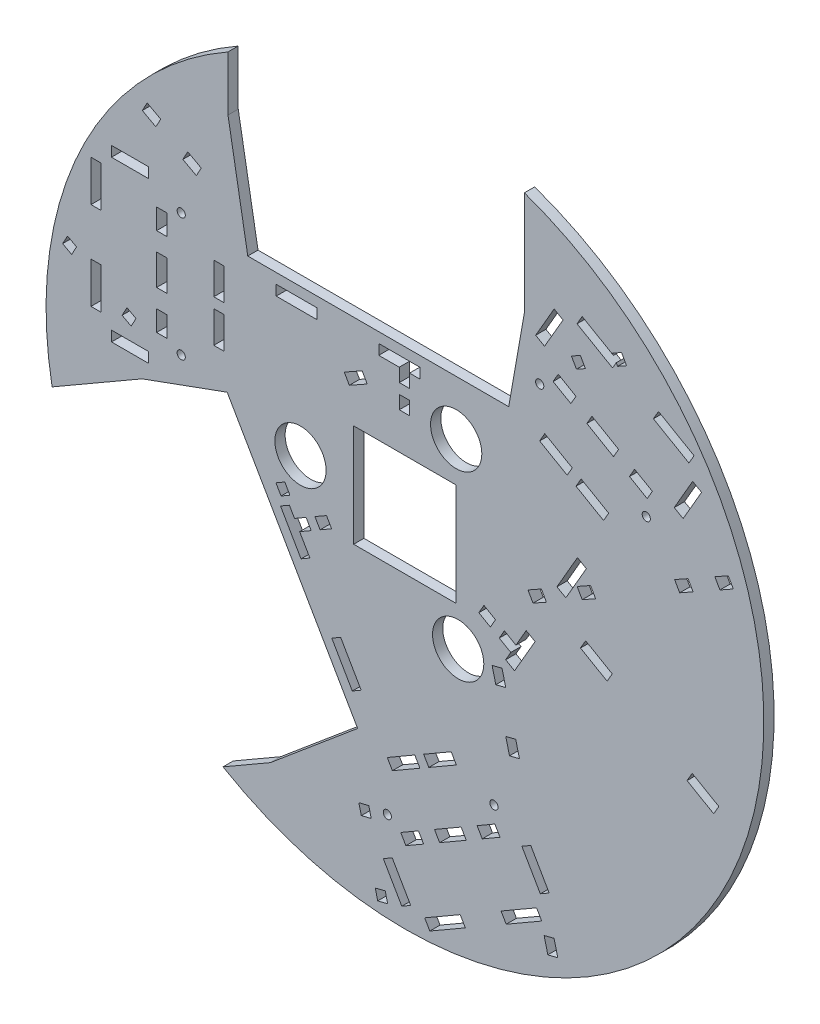
SolidWorks part; units mm, degrees
material "Balsa"
ref_plane "Plan de face" through (0, 0, 0) normal (0, 0, 1) x (1, 0, 0)
ref_plane "Plan de dessus" through (0, 0, 0) normal (0, 1, 0) x (1, 0, 0)
ref_plane "Plan de droite" through (0, 0, 0) normal (1, 0, 0) x (0, 0, -1)
sketch "Esquisse1" plane through (0, 0, 0) normal (0, 0, 1) x (1, 0, 0)
  circle A0 centre (148.0804, -12.1102) radius 175
  dimension "D1" = 350
extrude "Boss.-Extru.1" add sketch "Esquisse1" along normal blind 5
sketch "Esquisse2" plane through (0, 0, 5) normal (0, 0, 1) x (1, 0, 0)
  line L0 (135.3118, 53.7774) -> (135.3118, 48.7774)
  line L1 (5, 72.2774) -> (23, 72.2774)
  line L2 (5, 72.2774) -> (5, 67.2774)
  line L3 (5, 67.2774) -> (23, 67.2774)
  line L4 (23, 72.2774) -> (23, 67.2774)
  line L5 (-5, 62.2774) -> (0, 62.2774)
  line L6 (-5, 62.2774) -> (-5, 42.2774)
  line L7 (-5, 42.2774) -> (0, 42.2774)
  line L8 (0, 62.2774) -> (0, 42.2774)
  line L9 (-5, 19.2774) -> (0, 19.2774)
  line L10 (-5, 19.2774) -> (-5, -0.7226)
  line L11 (-5, -0.7226) -> (0, -0.7226)
  line L12 (0, 19.2774) -> (0, -0.7226)
  line L13 (5, -5.7226) -> (23, -5.7226)
  line L14 (5, -5.7226) -> (5, -10.7226)
  line L15 (5, -10.7226) -> (23, -10.7226)
  line L16 (23, -5.7226) -> (23, -10.7226)
  line L17 (27, 14.2774) -> (32, 14.2774)
  line L18 (27, 14.2774) -> (27, 4.2774)
  line L19 (27, 4.2774) -> (32, 4.2774)
  line L20 (32, 14.2774) -> (32, 4.2774)
  line L21 (27, 38.2774) -> (32, 38.2774)
  line L22 (27, 38.2774) -> (27, 23.2774)
  line L23 (27, 23.2774) -> (32, 23.2774)
  line L24 (32, 38.2774) -> (32, 23.2774)
  line L25 (27, 57.2774) -> (32, 57.2774)
  line L26 (27, 57.2774) -> (27, 47.2774)
  line L27 (27, 47.2774) -> (32, 47.2774)
  line L28 (32, 57.2774) -> (32, 47.2774)
  line L29 (54.86, 48.7774) -> (59.86, 48.7774)
  line L30 (54.86, 48.7774) -> (54.86, 33.2774)
  line L31 (54.86, 33.2774) -> (59.86, 33.2774)
  line L32 (59.86, 48.7774) -> (59.86, 33.2774)
  line L33 (54.86, 28.2774) -> (59.86, 28.2774)
  line L34 (54.86, 28.2774) -> (54.86, 12.7774)
  line L35 (54.86, 12.7774) -> (59.86, 12.7774)
  line L36 (59.86, 28.2774) -> (59.86, 12.7774)
  line L37 (85.3118, 53.7774) -> (105.3118, 53.7774)
  line L38 (85.3118, 53.7774) -> (85.3118, 48.7774)
  line L39 (85.3118, 48.7774) -> (105.3118, 48.7774)
  line L40 (105.3118, 53.7774) -> (105.3118, 48.7774)
  line L41 (145.3118, 37.2774) -> (150.3118, 37.2774)
  line L42 (145.3118, 37.2774) -> (145.3118, 30.7774)
  line L43 (145.3118, 30.7774) -> (150.3118, 30.7774)
  line L44 (150.3118, 37.2774) -> (150.3118, 30.7774)
  line L45 (135.3118, 48.7774) -> (145.3118, 48.7774)
  line L46 (155.3118, 48.7774) -> (135.3118, 48.7774) construction
  line L47 (145.3118, 48.7774) -> (145.3118, 42.2774)
  line L48 (145.3118, 42.2774) -> (150.3118, 42.2774)
  line L49 (150.3118, 42.2774) -> (150.3118, 48.7774)
  line L50 (150.3118, 48.7774) -> (155.3118, 48.7774)
  line L51 (155.3118, 48.7774) -> (155.3118, 53.7774)
  line L52 (155.3118, 53.7774) -> (135.3118, 53.7774)
  line L53 (292.7025, 69.6073) -> (283.7025, 54.0188)
  line L54 (292.7025, 69.6073) -> (288.3723, 72.1073)
  line L55 (288.3723, 72.1073) -> (279.3723, 56.5188)
  line L56 (283.7025, 54.0188) -> (279.3723, 56.5188)
  line L57 (289.0422, 83.2676) -> (286.5422, 78.9374)
  line L58 (289.0422, 83.2676) -> (271.7217, 93.2676)
  line L59 (271.7217, 93.2676) -> (269.2217, 88.9374)
  line L60 (286.5422, 78.9374) -> (269.2217, 88.9374)
  line L61 (251.8031, 104.7676) -> (249.3031, 100.4374)
  line L62 (251.8031, 104.7676) -> (234.4826, 114.7676)
  line L63 (234.4826, 114.7676) -> (231.9826, 110.4374)
  line L64 (249.3031, 100.4374) -> (231.9826, 110.4374)
  line L65 (225.1525, 108.6073) -> (216.1525, 93.0188)
  line L66 (225.1525, 108.6073) -> (220.8223, 111.1073)
  line L67 (220.8223, 111.1073) -> (211.8223, 95.5188)
  line L68 (216.1525, 93.0188) -> (211.8223, 95.5188)
  line L69 (231.473, 79.5547) -> (228.973, 75.2246)
  line L70 (231.473, 79.5547) -> (222.8127, 84.5547)
  line L71 (222.8127, 84.5547) -> (220.3127, 80.2246)
  line L72 (228.973, 75.2246) -> (220.3127, 80.2246)
  line L73 (252.2576, 67.5547) -> (249.7576, 63.2246)
  line L74 (252.2576, 67.5547) -> (239.2672, 75.0547)
  line L75 (239.2672, 75.0547) -> (236.7672, 70.7246)
  line L76 (249.7576, 63.2246) -> (236.7672, 70.7246)
  line L77 (268.7121, 58.0547) -> (266.2121, 53.7246)
  line L78 (268.7121, 58.0547) -> (260.0518, 63.0547)
  line L79 (260.0518, 63.0547) -> (257.5518, 58.7246)
  line L80 (266.2121, 53.7246) -> (257.5518, 58.7246)
  line L81 (247.4209, 38.1773) -> (244.9209, 33.8472)
  line L82 (247.4209, 38.1773) -> (233.9975, 45.9273)
  line L83 (233.9975, 45.9273) -> (231.4975, 41.5972)
  line L84 (244.9209, 33.8472) -> (231.4975, 41.5972)
  line L85 (229.6673, 48.4273) -> (227.1673, 44.0972)
  line L86 (229.6673, 48.4273) -> (216.2439, 56.1773)
  line L87 (216.2439, 56.1773) -> (213.7439, 51.8472)
  line L88 (227.1673, 44.0972) -> (213.7439, 51.8472)
  line L89 (211.5251, -33.996) -> (207.195, -31.496)
  line L90 (236.5251, 9.3053) -> (226.5251, -8.0153)
  line L91 (236.5251, 9.3053) -> (232.195, 11.8053)
  line L92 (232.195, 11.8053) -> (222.195, -5.5153)
  line L93 (226.5251, -8.0153) -> (222.195, -5.5153)
  line L94 (192.2357, -34.4063) -> (189.7357, -38.7364)
  line L95 (192.2357, -34.4063) -> (186.6065, -31.1563)
  line L96 (186.6065, -31.1563) -> (184.1065, -35.4864)
  line L97 (189.7357, -38.7364) -> (184.1065, -35.4864)
  line L98 (207.195, -31.496) -> (202.195, -40.1563)
  line L99 (202.195, -40.1563) -> (196.5658, -36.9063)
  line L100 (196.5658, -36.9063) -> (194.0658, -41.2364)
  line L101 (194.0658, -41.2364) -> (199.695, -44.4864)
  line L102 (199.695, -44.4864) -> (197.195, -48.8165)
  line L103 (197.195, -48.8165) -> (201.5251, -51.3165)
  line L104 (201.5251, -51.3165) -> (211.5251, -33.996)
  line L105 (146.5388, -178.2153) -> (137.5388, -162.6268)
  line L106 (146.5388, -178.2153) -> (150.869, -175.7153)
  line L107 (150.869, -175.7153) -> (141.869, -160.1268)
  line L108 (137.5388, -162.6268) -> (141.869, -160.1268)
  line L109 (160.1991, -181.8755) -> (157.6991, -177.5454)
  line L110 (160.1991, -181.8755) -> (177.5196, -171.8755)
  line L111 (177.5196, -171.8755) -> (175.0196, -167.5454)
  line L112 (157.6991, -177.5454) -> (175.0196, -167.5454)
  line L113 (197.4382, -160.3755) -> (194.9382, -156.0454)
  line L114 (197.4382, -160.3755) -> (214.7587, -150.3755)
  line L115 (214.7587, -150.3755) -> (212.2587, -146.0454)
  line L116 (194.9382, -156.0454) -> (212.2587, -146.0454)
  line L117 (214.0888, -139.2153) -> (205.0888, -123.6268)
  line L118 (214.0888, -139.2153) -> (218.4189, -136.7153)
  line L119 (218.4189, -136.7153) -> (209.4189, -121.1268)
  line L120 (205.0888, -123.6268) -> (209.4189, -121.1268)
  line L121 (185.7683, -130.1627) -> (183.2683, -125.8326)
  line L122 (185.7683, -130.1627) -> (194.4286, -125.1627)
  line L123 (194.4286, -125.1627) -> (191.9286, -120.8326)
  line L124 (183.2683, -125.8326) -> (191.9286, -120.8326)
  line L125 (164.9837, -142.1627) -> (162.4837, -137.8326)
  line L126 (164.9837, -142.1627) -> (177.9741, -134.6627)
  line L127 (177.9741, -134.6627) -> (175.4741, -130.3326)
  line L128 (162.4837, -137.8326) -> (175.4741, -130.3326)
  line L129 (148.5292, -151.6627) -> (146.0292, -147.3326)
  line L130 (148.5292, -151.6627) -> (157.1895, -146.6627)
  line L131 (157.1895, -146.6627) -> (154.6895, -142.3326)
  line L132 (146.0292, -147.3326) -> (154.6895, -142.3326)
  line L133 (141.9604, -123.2852) -> (139.4604, -118.9551)
  line L134 (141.9604, -123.2852) -> (155.3838, -115.5352)
  line L135 (155.3838, -115.5352) -> (152.8838, -111.2051)
  line L136 (139.4604, -118.9551) -> (152.8838, -111.2051)
  line L137 (159.7139, -113.0352) -> (157.2139, -108.7051)
  line L138 (159.7139, -113.0352) -> (173.1373, -105.2852)
  line L139 (173.1373, -105.2852) -> (170.6373, -100.9551)
  line L140 (157.2139, -108.7051) -> (170.6373, -100.9551)
  line L141 (97.4044, -56.1119) -> (101.7345, -53.6119)
  line L142 (122.4044, -99.4132) -> (112.4044, -82.0927)
  line L143 (122.4044, -99.4132) -> (126.7345, -96.9132)
  line L144 (126.7345, -96.9132) -> (116.7345, -79.5927)
  line L145 (112.4044, -82.0927) -> (116.7345, -79.5927)
  line L146 (106.6938, -39.2017) -> (104.1938, -34.8716)
  line L147 (106.6938, -39.2017) -> (112.323, -35.9517)
  line L148 (112.323, -35.9517) -> (109.823, -31.6216)
  line L149 (104.1938, -34.8716) -> (109.823, -31.6216)
  line L150 (101.7345, -53.6119) -> (96.7345, -44.9517)
  line L151 (96.7345, -44.9517) -> (102.3637, -41.7017)
  line L152 (102.3637, -41.7017) -> (99.8637, -37.3716)
  line L153 (99.8637, -37.3716) -> (94.2345, -40.6216)
  line L154 (94.2345, -40.6216) -> (91.7345, -36.2914)
  line L155 (91.7345, -36.2914) -> (87.4044, -38.7914)
  line L156 (87.4044, -38.7914) -> (97.4044, -56.1119)
  line L157 (135.3118, 53.7774) -> (135.3118, 48.7774) construction
  line L158 (105.3118, 53.7774) -> (135.3118, 53.7774) construction
  point P83 (148.0804, -12.1102)
  point P192 (148.0804, -12.1102)
  point P193 (148.0804, -12.1102)
  dimension "D1" = 3
extrude "Enlèv. mat.-Extru.1" cut sketch "Esquisse2" against normal blind 5
sketch "Esquisse6" plane through (0, 0, 5) normal (0, 0, 1) x (1, 0, 0)
  line L0 (93.9998, -7.2151) -> (100.2998, -18.127) construction
  line L1 (206.3213, 102.2219) -> (206.3213, 185.5637)
  line L2 (123.0804, -37.1102) -> (173.0804, -37.1102)
  line L3 (123.0804, -37.1102) -> (123.0804, 12.8898)
  line L4 (123.0804, 12.8898) -> (173.0804, 12.8898)
  line L5 (173.0804, -37.1102) -> (173.0804, 12.8898)
  line L6 (123.0804, -37.1102) -> (173.0804, 12.8898) construction
  line L7 (123.0804, 12.8898) -> (173.0804, -37.1102) construction
  line L8 (206.3213, 185.5637) -> (61.7972, 185.5637)
  line L9 (61.7972, 113.4862) -> (71.4438, 58.7774)
  line L10 (71.4438, 58.7774) -> (198.6608, 58.7774)
  line L11 (198.6608, 58.7774) -> (206.3213, 102.2219)
  line L12 (61.7972, 185.5637) -> (61.7972, 113.4862)
  line L13 (19.9456, -18.8381) -> (-52.2306, -60.5091)
  line L14 (-52.2306, -60.5091) -> (20.0314, -185.6706)
  line L15 (82.4524, -149.6318) -> (125.0083, -113.9232)
  line L16 (125.0083, -113.9232) -> (61.3998, -3.7501)
  line L17 (61.3998, -3.7501) -> (19.9456, -18.8381)
  line L18 (20.0314, -185.6706) -> (82.4524, -149.6318)
  line L19 (87.4044, -38.7914) -> (97.4044, -56.1119) construction
  line L20 (236.1714, -21.3074) -> (249.1617, -28.8074)
  line L21 (236.1714, -21.3074) -> (233.6714, -25.6375)
  line L22 (249.1617, -28.8074) -> (246.6617, -33.1375)
  line L23 (233.6714, -25.6375) -> (246.6617, -33.1375)
  line L24 (288.1329, -51.3074) -> (301.1233, -58.8074)
  line L25 (288.1329, -51.3074) -> (285.6329, -55.6375)
  line L26 (301.1233, -58.8074) -> (298.6233, -63.1375)
  line L27 (285.6329, -55.6375) -> (298.6233, -63.1375)
  line L28 (226.5251, -8.0153) -> (236.5251, 9.3053) construction
  line L29 (279.3723, 56.5188) -> (283.7025, 54.0188) construction
  circle A0 centre (173.06, 32.2774) radius 12.5
  circle A1 centre (174.0314, -55.9369) radius 12.5
  circle A2 centre (97.1498, -12.671) radius 12.5
  point P2 (148.0804, -12.1102)
  point P8 (148.0804, -12.1102)
  point P10 (148.0804, -12.1102)
  point P35 (148.0804, -12.1102)
  dimension "D2" = 25
  dimension "D3" = 50
  dimension "D4" = 50
  dimension "D5" = 70.8876
  dimension "D6" = 50.5804
  dimension "D7" = 127.217
  dimension "D8" = 100
  dimension "D9" = 100
  dimension "D10" = 54.7088
  dimension "D11" = 43.4444
  dimension "D13" = 5
  dimension "D14" = 15
  dimension "D15" = 15
  dimension "D16" = 45
  dimension "D17" = 15
  dimension "D18" = 89
  dimension "D1" = 3
  dimension "D12" = 2
extrude "Enlèv. mat.-Extru.6" cut sketch "Esquisse6" against normal blind 5
hole_wizard "Trous de centrage Ø4.0mm1" positions "Esquisse7" profile "Esquisse8" hole size "Ø4.0" standard "Ansi Metric" end condition through all
sketch "Esquisse7" plane through (148.0804, -12.1102, -78) normal (0, 0, -1) x (1, 0, 0)
  point P0 (65.7012, -88.0226)
  point P3 (117.6627, -58.0226)
  point P6 (-109.0804, -72.8876)
  point P9 (-109.0804, -12.8876)
  point P12 (-8.5823, 130.9102)
  point P15 (43.3792, 100.9102)
sketch "Esquisse8" plane through (213.7816, 75.9124, -78) normal (1, 0, 0) x (0, 1, 0)
  line L0 (0, 0) -> (0, 83)
  line L1 (0, 83) -> (2, 83)
  line L2 (2, 83) -> (2, 0)
  line L3 (2, 0) -> (0, 0)
  line L4 (0, -6.35) -> (0, 107.95) construction
  dimension "Diamètre du perçage jusqu'au prochain" = 4
  dimension "Profondeur du perçage jusqu'au prochain" = 83
sketch "Esquisse9" plane through (0, 0, 5) normal (0, 0, 1) x (1, 0, 0)
  line L0 (301.6473, 32.8747) -> (299.2005, 37.2351)
  line L1 (301.6473, 32.8747) -> (308.1879, 36.5449)
  line L2 (299.2005, 37.2351) -> (305.7411, 40.9053)
  line L3 (308.1879, 36.5449) -> (305.7411, 40.9053)
  line L4 (282.0254, 21.8642) -> (279.5786, 26.2246)
  line L5 (282.0254, 21.8642) -> (288.566, 25.5344)
  line L6 (279.5786, 26.2246) -> (286.1192, 29.8948)
  line L7 (288.566, 25.5344) -> (286.1192, 29.8948)
  line L8 (241.0375, -1.1356) -> (238.5907, 3.2248)
  line L9 (241.0375, -1.1356) -> (234.4969, -4.8058)
  line L10 (238.5907, 3.2248) -> (232.0501, -0.4454)
  line L11 (234.4969, -4.8058) -> (232.0501, -0.4454)
  line L12 (214.6084, -10.2326) -> (217.0552, -14.593)
  line L13 (214.6084, -10.2326) -> (208.0678, -13.9027)
  line L14 (217.0552, -14.593) -> (210.5146, -18.2632)
  line L15 (208.0678, -13.9027) -> (210.5146, -18.2632)
  line L16 (217.0552, -14.593) -> (234.4969, -4.8058) construction
  line L17 (214.6084, -10.2326) -> (217.0552, -14.593) construction
  line L18 (256.1275, 104.7997) -> (251.7671, 102.3529)
  line L19 (256.1275, 104.7997) -> (253.6807, 109.1601)
  line L20 (251.7671, 102.3529) -> (249.3203, 106.7133)
  line L21 (253.6807, 109.1601) -> (249.3203, 106.7133)
  line L22 (236.0696, 93.5445) -> (231.7091, 91.0977)
  line L23 (236.0696, 93.5445) -> (233.6228, 97.9049)
  line L24 (231.7091, 91.0977) -> (229.2624, 95.4581)
  line L25 (233.6228, 97.9049) -> (229.2624, 95.4581)
  line L26 (129.6754, 33.8428) -> (120.9546, 28.9492)
  line L27 (129.6754, 33.8428) -> (127.2286, 38.2032)
  line L28 (120.9546, 28.9492) -> (118.5078, 33.3096)
  line L29 (127.2286, 38.2032) -> (118.5078, 33.3096)
  line L30 (256.1275, 104.7997) -> (120.9546, 28.9492) construction
  line L31 (301.6473, 32.8747) -> (217.0552, -14.593) construction
  line L32 (-16.4384, 23.2791) -> (-12.0459, 20.8904)
  line L33 (-16.4384, 23.2791) -> (-18.8272, 18.8866)
  line L34 (-12.0459, 20.8904) -> (-14.4347, 16.4979)
  line L35 (-18.8272, 18.8866) -> (-14.4347, 16.4979)
  line L36 (12.552, 7.5136) -> (16.9445, 5.1249)
  line L37 (12.552, 7.5136) -> (10.1633, 3.1211)
  line L38 (16.9445, 5.1249) -> (14.5558, 0.7324)
  line L39 (10.1633, 3.1211) -> (14.5558, 0.7324)
  line L44 (22.4127, 98.9071) -> (29.0015, 95.324)
  line L45 (22.4127, 98.9071) -> (20.024, 94.5146)
  line L46 (29.0015, 95.324) -> (26.6128, 90.9315)
  line L47 (20.024, 94.5146) -> (26.6128, 90.9315)
  line L48 (42.179, 88.1579) -> (48.7677, 84.5748)
  line L49 (42.179, 88.1579) -> (39.7903, 83.7654)
  line L50 (48.7677, 84.5748) -> (46.379, 80.1823)
  line L51 (39.7903, 83.7654) -> (46.379, 80.1823)
  line L53 (148.0804, -12.1102) -> (9.6568, -109.2191) construction
  line L55 (130.4208, 187.6926) -> (148.0804, -12.1102) construction
  arc A0 (59.3693, -162.9589) -> (206.3213, 152.9141) centre (148.0804, -12.1102) ccw construction
  line B0 (154.106, -73.5915) -> (185.6214, -199.5155) construction
  line B1 (126.7996, -149.8343) -> (125.5857, -144.9839)
  line B2 (130.4361, -143.77) -> (125.5857, -144.9839)
  line B3 (131.65, -148.6204) -> (126.7996, -149.8343)
  line B4 (131.65, -148.6204) -> (130.4361, -143.77)
  line B5 (134.8115, -181.8469) -> (133.5976, -176.9965)
  line B6 (138.448, -175.7826) -> (133.5976, -176.9965)
  line B7 (139.6619, -180.633) -> (134.8115, -181.8469)
  line B8 (139.6619, -180.633) -> (138.448, -175.7826)
  line B9 (190.562, -54.5014) -> (195.4124, -53.2875)
  line B10 (197.2333, -60.5631) -> (195.4124, -53.2875)
  line B11 (192.3829, -61.777) -> (190.562, -54.5014)
  line B12 (192.3829, -61.777) -> (197.2333, -60.5631)
  line B13 (202.089, -79.9647) -> (197.2386, -81.1786)
  line B14 (199.0595, -88.4542) -> (197.2386, -81.1786)
  line B15 (203.9099, -87.2403) -> (202.089, -79.9647)
  line B16 (203.9099, -87.2403) -> (199.0595, -88.4542)
  line B17 (222.6043, -161.9364) -> (217.7539, -163.1503)
  line B18 (215.933, -155.8747) -> (217.7539, -163.1503)
  line B19 (220.7834, -154.6608) -> (222.6043, -161.9364)
  line B20 (220.7834, -154.6608) -> (215.933, -155.8747)
  dimension "D9" = 170.2546
  dimension "D1" = 10
  dimension "D2" = 5
  dimension "D3" = 7.5
  dimension "D4" = 7.5
  dimension "D5" = 7.5
  dimension "D6" = 7.5
  dimension "D7" = 5
  dimension "D8" = 117
  dimension "D10" = 167.3371
  dimension "D11" = 69
sketch_block_instance "Bloc1-1"
sketch_block "Bloc1"
extrude "Holes catchers of glass" cut sketch "Esquisse9" against normal blind 10
sketch "Esquisse10" plane through (0, 0, 5) normal (0, 0, 1) x (1, 0, 0)
  line L0 (89.4961, -27.6144) -> (91.9961, -31.9445)
  line L1 (89.4961, -27.6144) -> (85.1672, -30.1137)
  line L2 (91.9961, -31.9445) -> (87.6672, -34.4438)
  line L3 (85.1672, -30.1137) -> (87.6672, -34.4438)
  dimension "D1" = 4.9986
extrude "Holes boards servo" cut sketch "Esquisse10" against normal blind 10
